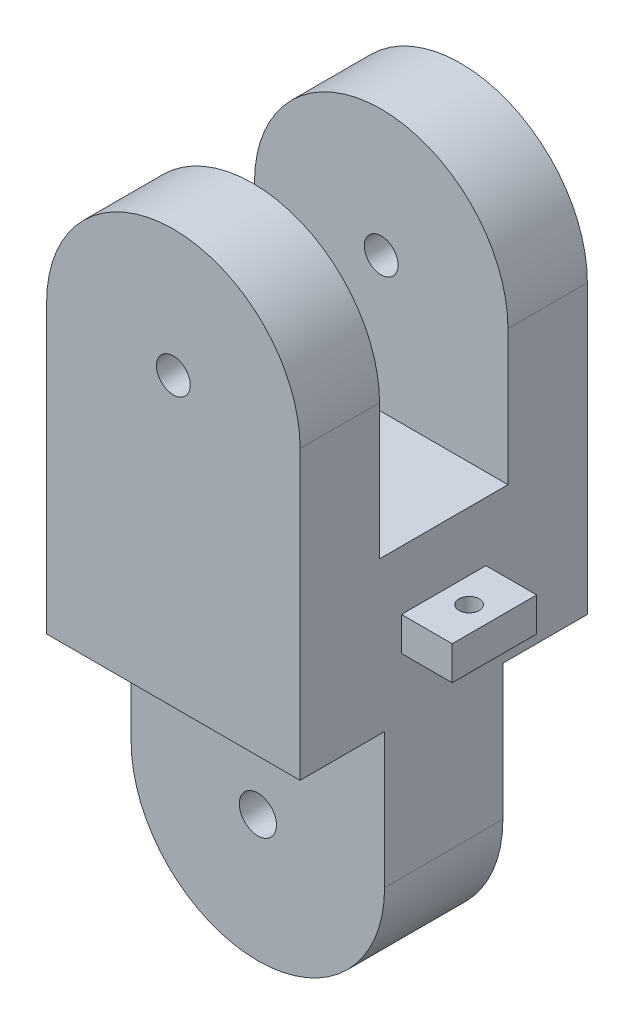
SolidWorks part; units mm, degrees
ref_plane "Front Plane" through (0, 0, 0) normal (0, 0, 1) x (1, 0, 0)
ref_plane "Top Plane" through (0, 0, 0) normal (0, 1, 0) x (1, 0, 0)
ref_plane "Right Plane" through (0, 0, 0) normal (1, 0, 0) x (0, 0, -1)
sketch "Finger_Skeleton" plane through (0, 0, 0) normal (0, 0, -1) x (-1, 0, 0)
  line L0 (0, 0) -> (0, 25)
  line L1 (0, 25) -> (0, 50)
  line L2 (0, 50) -> (0, 73)
  circle A1 centre (0, 0) radius 5 construction
  circle A2 centre (0, 25) radius 5 construction
  circle A3 centre (0, 50) radius 5 construction
  point P3 (0, 0)
  point P9 (0, 0)
  dimension "D4" = 10
  dimension "D5" = 10
  dimension "D6" = 10
  dimension "D1" = 25
  dimension "D2" = 25
  dimension "D3" = 23
sketch "Link1_Outline" plane through (0, 0, 0) normal (0, 0, 1) x (1, 0, 0)
  line L0 (0, 0) -> (0, 25) construction
  line L1 (-7.5, 0) -> (-7.5, 25)
  line L2 (7.5, 0) -> (7.5, 25)
  arc A0 (-7.5, 0) -> (7.5, 0) centre (0, 0) ccw
  arc A1 (7.5, 25) -> (-7.5, 25) centre (0, 25) ccw
  point P4 (0, 12.5)
  dimension "D1" = 15
extrude "Link1_Body" add sketch "Link1_Outline" along normal mid plane 17
sketch "Sketch1" plane through (7.5, 0, 0) normal (1, 0, 0) x (0, 0, -1)
  line L0 (0, 0) -> (0, 25) construction
  line L1 (3.5, -8) -> (9, -8)
  line L2 (3.5, -8) -> (3.5, 7.9981)
  line L3 (3.5, 7.9981) -> (9, 7.9981)
  line L4 (9, -8) -> (9, 7.9981)
  line L5 (-8.5, -7.5) -> (8.5, -7.5) construction
  line L6 (0, 5.5) -> (0, -5.5) construction
  line L7 (-9, -8) -> (-9, 7.9981)
  line L8 (-3.5, 7.9981) -> (-9, 7.9981)
  line L9 (-3.5, -8) -> (-3.5, 7.9981)
  line L10 (-3.5, -8) -> (-9, -8)
  dimension "D1" = 3.5
  dimension "D2" = 5.5
  dimension "D3" = 15.9981
  dimension "D4" = 0.5
extrude "Tongue_Cut" cut sketch "Sketch1" against normal through all both and the other way through all
sketch "Sketch2" plane through (0, 0, 0) normal (1, 0, 0) x (0, 0, -1)
  line L0 (0, 0) -> (0, 25) construction
  line L1 (3.8, 17) -> (-3.8, 17)
  line L2 (3.8, 17) -> (3.8, 35)
  line L3 (3.8, 35) -> (-3.8, 35)
  line L4 (-3.8, 17) -> (-3.8, 35)
  dimension "D1" = 3.8
  dimension "D2" = 18
  dimension "D3" = 7.6
  dimension "D4" = 17
extrude "Slot_Cut" cut sketch "Sketch2" against normal through all both and the other way through all
sketch "Sketch3" plane through (0, 0, 0) normal (0, 0, 1) x (1, 0, 0)
  circle A0 centre (0, 0) radius 1.1
  circle A1 centre (0, 25) radius 1
  dimension "D1" = 2.2
  dimension "D2" = 2
extrude "Pin_Holes" cut sketch "Sketch3" against normal through all both and the other way through all
sketch "Sketch4" plane through (0, 0, 0) normal (0, 0, 1) x (1, 0, 0)
  line L0 (0, 0) -> (0, 25) construction
  line L1 (7, 13.5) -> (10.5, 13.5)
  line L2 (7, 13.5) -> (7, 11.5)
  line L3 (7, 11.5) -> (10.5, 11.5)
  line L4 (10.5, 13.5) -> (10.5, 11.5)
  dimension "D1" = 7
  dimension "D2" = 3.5
  dimension "D3" = 11.5
  dimension "D4" = 2
extrude "Guide_Block_1" add sketch "Sketch4" along normal mid plane 5
sketch "Sketch5" plane through (0, 0, 0) normal (0, 0, 1) x (1, 0, 0)
  line L0 (0, 0) -> (0, 25) construction
  line L1 (7.0006, 32) -> (10.5006, 32)
  line L2 (7.0006, 32) -> (7.0006, 34)
  line L3 (7.0006, 34) -> (10.5006, 34)
  line L4 (10.5006, 32) -> (10.5006, 34)
  dimension "D1" = 7.0006
  dimension "D2" = 32
  dimension "D3" = 3.5
  dimension "D4" = 2
sketch "Sketch6" plane through (0, 0, 0) normal (0, 1, 0) x (1, 0, 0)
  line L1 (10.5, -2.5) -> (7.5, -2.5) construction
  circle A0 centre (9, 0) radius 0.6
  point P5 (0, 0)
  dimension "D1" = 1.2
  dimension "D2" = 9
  dimension "D3" = 2.5
extrude "Cord_Guides" cut sketch "Sketch6" along normal through all both and the other way through all
